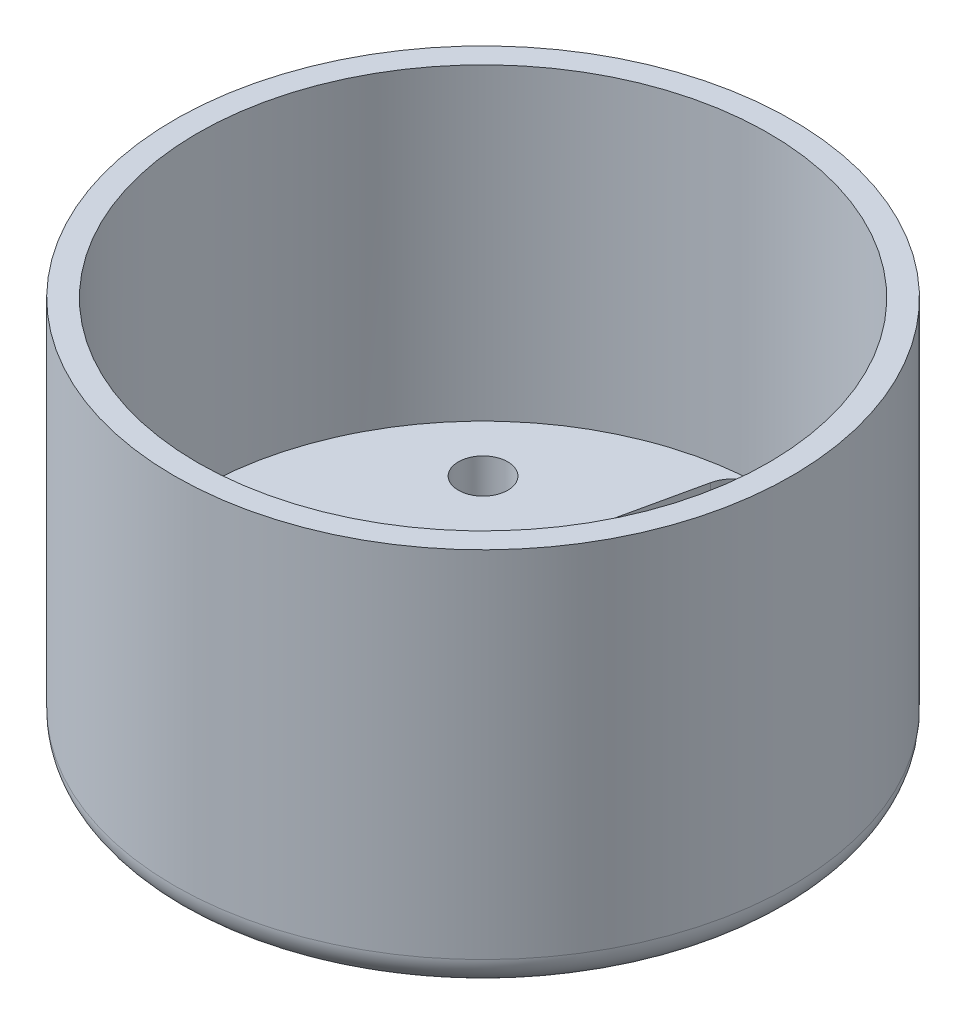
SolidWorks part; units mm, degrees
material "自定义塑料"
ref_plane "前视基准面" through (0, 0, 0) normal (0, 0, 1) x (1, 0, 0)
ref_plane "上视基准面" through (0, 0, 0) normal (0, 1, 0) x (1, 0, 0)
ref_plane "右视基准面" through (0, 0, 0) normal (1, 0, 0) x (0, 0, -1)
sketch "草图1" plane through (0, 0, 0) normal (0, 1, 0) x (1, 0, 0)
  circle A0 centre (0, 0) radius 4.7
  circle A1 centre (0, 0) radius 20
extrude "凸台-拉伸1" add sketch "草图1" along normal blind 2.5
sketch "草图2" plane through (0, 2.5, 0) normal (0, 1, 0) x (1, 0, 0)
  line L0 (0, 0) -> (0, -6)
  line L1 (0, 0) -> (-24.9951, -0.4942)
  line L2 (0, -6) -> (-17.0041, -2.2544)
  line L3 (0, 0) -> (0, 6)
  line L4 (0, 6) -> (-17.0756, 1.5634)
  line L5 (0, 0) -> (-18.4964, -0.3657)
  line L6 (-18.4964, -0.3657) -> (-18.4974, -0.3131)
  line L7 (-18.4974, -0.3131) -> (-18.495, -0.4365)
  line L8 (6, 0) -> (1.5634, 17.0756)
  line L9 (-6, 0) -> (-2.2544, 17.0041)
  line L10 (-0.3657, 18.4964) -> (-0.3131, 18.4974)
  line L11 (0, -6) -> (17.0756, -1.5634)
  line L12 (0, 6) -> (17.0041, 2.2544)
  line L13 (18.4964, 0.3657) -> (18.4974, 0.3131)
  line L14 (-6, 0) -> (-1.5634, -17.0756)
  line L15 (6, 0) -> (2.2544, -17.0041)
  line L16 (0.3657, -18.4964) -> (0.3131, -18.4974)
  arc A0 (-17.0041, -2.2544) -> (-18.495, -0.4365) centre (-16.5954, -0.3989) cw
  arc A1 (-17.0756, 1.5634) -> (-18.4974, -0.3131) centre (-16.5978, -0.2755) ccw
  circle A2 centre (0, 0) radius 18.5
  arc A3 (1.5634, 17.0756) -> (-0.3131, 18.4974) centre (-0.2755, 16.5978) ccw
  arc A4 (-2.2544, 17.0041) -> (-0.4365, 18.495) centre (-0.3989, 16.5954) cw
  arc A5 (17.0756, -1.5634) -> (18.4974, 0.3131) centre (16.5978, 0.2755) ccw
  arc A6 (17.0041, 2.2544) -> (18.495, 0.4365) centre (16.5954, 0.3989) cw
  arc A7 (-1.5634, -17.0756) -> (0.3131, -18.4974) centre (0.2755, -16.5978) ccw
  arc A8 (2.2544, -17.0041) -> (0.4365, -18.495) centre (0.3989, -16.5954) cw
  point P43 (0, 0)
  dimension "D1" = 1.9
  dimension "D2" = 4
extrude "凸台-拉伸2" add sketch "草图2" along normal blind 2.5 contours L12 A6 A2 A3 L8 | A7 A2 A0 L7 L6 A1 L10 A3 L13 A5 L16 | L9 A4 A2 A1 L4 | A7 L14 L2 A0 A2 | L15 A8 A2 A5 L11 region at (-9.4133, 2.5, 9.8122) region at (9.8121, 2.5, 9.4133) region at (-0.1921, 2.5, -19.4334) region at (-9.8121, 2.5, -9.4133) region at (9.4133, 2.5, -9.8121)
fillet "圆角1" radius 5 4 edges at (-4.7107, 3.75, 4.9624) (-4.9624, 3.75, -4.7107) (4.9624, 3.75, 4.7107) (4.7107, 3.75, -4.9624)
sketch "草图3" plane through (0, 5, 0) normal (0, 1, 0) x (1, 0, 0)
  circle A0 centre (0, 0) radius 20
  circle A1 centre (0, 0) radius 18.5001
extrude "凸台-拉伸3" add sketch "草图3" along normal blind 20
sketch "草图4" plane through (0, 0, 0) normal (0, -1, 0) x (1, 0, 0)
  line L0 (-10, -6.6514) -> (-12.9, -8.3257)
  line L1 (10, -10) -> (-10, -10)
  line L2 (10, -10) -> (10, 10)
  line L3 (10, 10) -> (-10, 10)
  line L4 (-10, -10) -> (-10, 10)
  line L5 (10, -10) -> (-10, 10) construction
  line L6 (10, 10) -> (-10, -10) construction
  line L7 (6.6514, -10) -> (8.3257, -12.9)
  line L8 (8.3257, -12.9) -> (11.6743, -12.9)
  line L9 (11.6743, -12.9) -> (13.3486, -10)
  line L10 (13.3486, -10) -> (11.6743, -7.1)
  line L11 (11.6743, -7.1) -> (8.3257, -7.1)
  line L12 (8.3257, -7.1) -> (6.6514, -10)
  line L13 (-12.9, -8.3257) -> (-12.9, -11.6743)
  line L14 (-12.9, -11.6743) -> (-10, -13.3486)
  line L15 (-10, -13.3486) -> (-7.1, -11.6743)
  line L16 (-7.1, -11.6743) -> (-7.1, -8.3257)
  line L17 (-7.1, -8.3257) -> (-10, -6.6514)
  line L18 (-6.6514, 10) -> (-8.3257, 12.9)
  line L19 (-8.3257, 12.9) -> (-11.6743, 12.9)
  line L20 (-11.6743, 12.9) -> (-13.3486, 10)
  line L21 (-13.3486, 10) -> (-11.6743, 7.1)
  line L22 (-11.6743, 7.1) -> (-8.3257, 7.1)
  line L23 (-8.3257, 7.1) -> (-6.6514, 10)
  line L24 (10, 6.6514) -> (12.9, 8.3257)
  line L25 (12.9, 8.3257) -> (12.9, 11.6743)
  line L26 (12.9, 11.6743) -> (10, 13.3486)
  line L27 (10, 13.3486) -> (7.1, 11.6743)
  line L28 (7.1, 11.6743) -> (7.1, 8.3257)
  line L29 (7.1, 8.3257) -> (10, 6.6514)
  circle A0 centre (10, -10) radius 2.9 construction
  point P0 (0, 0)
  point P34 (0, 0)
  dimension "D1" = 20
  dimension "D2" = 4
extrude "切除-拉伸1" cut sketch "草图4" against normal blind 2.6 contours L10 L11 L2 L1 L7 L8 L9 | L11 L12 L1 L2 | L16 L17 L4 L1 | L15 L16 L1 L4 L0 L13 L14 | L21 L22 L4 L3 L18 L19 L20 | L22 L23 L3 L4 | L27 L28 L3 L2 L24 L25 L26 | L28 L29 L2 L3 region at (-10.4296, 0, -10.4341) region at (-8.7111, 0, -8.6978) region at (-10.4341, 0, 10.4296) region at (-8.6978, 0, 8.7111) region at (8.6978, 0, -8.7111) region at (10.4341, 0, -10.4296) region at (10.4296, 0, 10.4341) region at (8.7111, 0, 8.6978)
sketch "草图5" plane through (0, 2.6, 0) normal (0, -1, 0) x (1, 0, 0)
  circle A0 centre (10, -10) radius 1.6
  circle A1 centre (-10, -10) radius 1.6
  circle A2 centre (-10, 10) radius 1.6
  circle A3 centre (10, 10) radius 1.6
  point P11 (0, 0)
  dimension "D1" = 4
extrude "切除-拉伸2" cut sketch "草图5" against normal blind 2.6
fillet "圆角2" radius 2 1 edges at (0, 0, 20)
